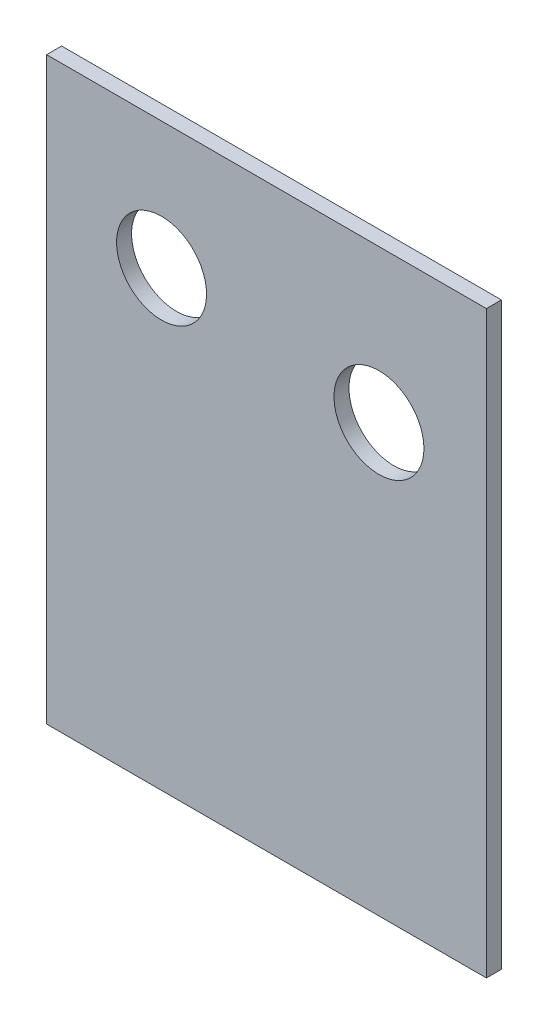
SolidWorks part; units mm, degrees
ref_plane "Front Plane" through (0, 0, 0) normal (0, 0, 1) x (1, 0, 0)
ref_plane "Top Plane" through (0, 0, 0) normal (0, 1, 0) x (1, 0, 0)
ref_plane "Right Plane" through (0, 0, 0) normal (1, 0, 0) x (0, 0, -1)
sketch "Sketch1" plane through (0, 0, 0) normal (0, 0, 1) x (1, 0, 0)
  line L1 (-44, -58) -> (44, -58)
  line L2 (-44, -58) -> (-44, 58)
  line L3 (-44, 58) -> (44, 58)
  line L4 (44, -58) -> (44, 58)
  line L5 (-44, -58) -> (44, 58) construction
  line L6 (-44, 58) -> (44, -58) construction
  circle A0 centre (-22.8181, 25.0296) radius 20 construction
  circle A1 centre (24.0245, 19.8034) radius 20 construction
  point P0 (0, 0)
  point P8 (-14.6566, 33.443)
  point P9 (-33.2705, 29.6752)
  point P12 (32.9284, 21.3519)
  point P13 (-27.27, 24.2554)
  point P14 (27.8958, 19.8034)
  point P15 (-22.8181, 25.0296)
  point P16 (24.0245, 19.8034)
  dimension "D3" = 40
  dimension "D1" = 88
  dimension "D2" = 116
extrude "Boss-Extrude1" add sketch "Sketch1" along normal blind 3 contours L3 L4 L1 L2
sketch "Sketch2" plane through (0, 0, 3) normal (0, 0, 1) x (1, 0, 0)
  line L0 (-44, -58) -> (-44, 58) construction
  line L1 (-44, 58) -> (44, 58) construction
  circle A0 centre (-21, 32.5) radius 20 construction
  circle A1 centre (22.5, 27.5) radius 20 construction
  circle A2 centre (-21, 32.5) radius 9
  circle A3 centre (22.5, 27.5) radius 9
  dimension "D1" = 23
  dimension "D2" = 40
  dimension "D3" = 43.5
  dimension "D6" = 18
  dimension "D4" = 25.5
  dimension "D5" = 5
extrude "Cut-Extrude1" cut sketch "Sketch2" against normal through all
